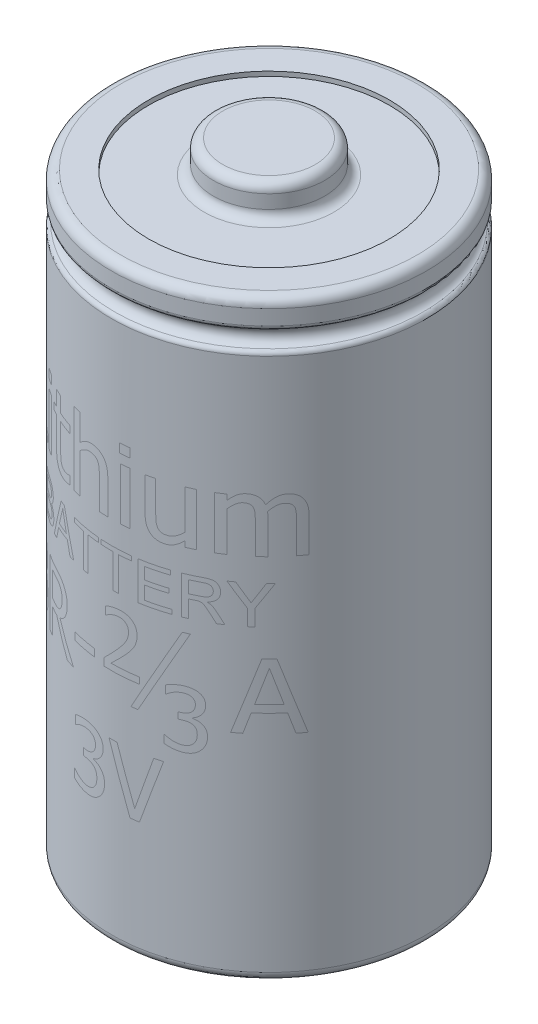
SolidWorks part; units mm, degrees
ref_plane "Front" through (0, 0, 0) normal (0, 0, 1) x (1, 0, 0)
ref_plane "Top" through (0, 0, 0) normal (0, 1, 0) x (1, 0, 0)
ref_plane "Right" through (0, 0, 0) normal (1, 0, 0) x (0, 0, -1)
sketch "Sketch1" plane through (0, 0, 0) normal (0, 0, 1) x (1, 0, 0)
  line L0 (0, -4.0826) -> (0, 56.434) construction
  line L1 (8.5, 30.7071) -> (8.5, 31.52)
  line L2 (6.5, 0) -> (6.5, 0.25)
  line L3 (0, 0.25) -> (0, 33.5)
  line L4 (8.5, 0.5) -> (8.5, 29.2929)
  line L5 (6.5, 0.25) -> (0, 0.25)
  line L7 (3, 32.27) -> (3, 33)
  line L8 (2.5, 33.5) -> (0, 33.5)
  line L11 (6.5, 32.02) -> (8, 32.02)
  line L12 (6.5, 31.77) -> (6.5, 32.02)
  line L15 (6.5, 0) -> (8, 0)
  line L16 (3.5, 31.77) -> (6.5, 31.77)
  arc A0 (3, 33) -> (2.5, 33.5) centre (2.5, 33) ccw
  arc A1 (3, 32.27) -> (3.5, 31.77) centre (3.5, 32.27) ccw
  arc A2 (8, 32.02) -> (8.5, 31.52) centre (8, 31.52) cw
  arc A3 (8.3333, 30.4714) -> (8.3333, 29.5286) centre (8.5, 30) ccw
  arc A4 (8.5, 30.7071) -> (8.3333, 30.4714) centre (8.25, 30.7071) cw
  arc A5 (8.5, 29.2929) -> (8.3333, 29.5286) centre (8.25, 29.2929) ccw
  arc A6 (8.5, 0.5) -> (8, 0) centre (8, 0.5) cw
  point P17 (8.5, 32.02)
  point P21 (8.5, 0)
  point P28 (8.5, 0)
  dimension "D8" = 0.25
  dimension "D9" = 1
  dimension "D10" = 0.25
  dimension "D11" = 0.25
  dimension "D2" = 0.5
  dimension "D3" = 0.5
  dimension "D5" = 8.5
  dimension "D12" = 0.5
  dimension "D4" = 1.48
  dimension "D6" = 3
  dimension "D7" = 2
  dimension "D13" = 0.25
  dimension "D14" = 33.5
  dimension "D15" = 3.5
revolve "Revolve1" add sketch "Sketch1" angle 360 about L0
ref_plane "Plane1" through (0, 0, 8.5) normal (0, 0, 1) x (1, 0, 0)
sketch "Sketch3" plane through (0, 0, 8.5) normal (0, 0, 1) x (1, 0, 0)
  line L0 (3.2741, 15.9258) -> (0.9929, 11.6354)
  line L1 (0.9929, 11.6354) -> (1.3277, 11.6354)
  line L2 (1.3277, 11.6354) -> (3.609, 15.9258)
  line L3 (3.609, 15.9258) -> (3.2741, 15.9258)
  text T0 "Lithium" font "Tahoma" height in points 14
  text T1 "BATTERY" font "Arial" height in points 8
  text T2 "BR-    A" font "Tahoma" height in points 13
  text T3 "2" font "Tahoma" height in points 11
  text T4 "3" font "Tahoma" height in points 11
  text T5 "3V" font "Tahoma" height in points 12
wrap "Wrap1" sketch "Sketch3" wrap type scribe source sketch "Sketch3" face at (0, 29.2929, -8.5)
